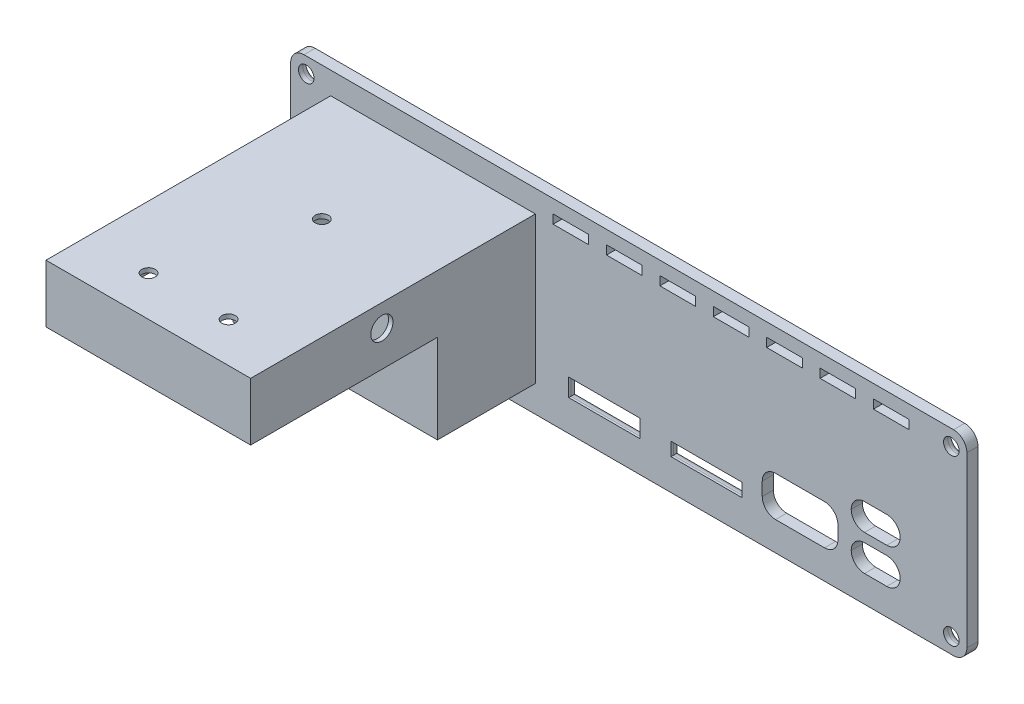
SolidWorks part; units mm, degrees
ref_plane "Front Plane" through (0, 0, 0) normal (0, 0, 1) x (1, 0, 0)
ref_plane "Top Plane" through (0, 0, 0) normal (0, 1, 0) x (1, 0, 0)
ref_plane "Right Plane" through (0, 0, 0) normal (1, 0, 0) x (0, 0, -1)
sketch "Sketch1" plane through (0, 0, 0) normal (0, 0, 1) x (1, 0, 0)
  line L1 (76, -22) -> (-76, -22)
  line L2 (76, -22) -> (76, 22)
  line L3 (76, 22) -> (-76, 22)
  line L4 (-76, -22) -> (-76, 22)
  line L5 (76, -22) -> (-76, 22) construction
  line L6 (76, 22) -> (-76, -22) construction
  point P0 (0, 0)
  dimension "D1" = 152
  dimension "D2" = 44
extrude "main_body" add sketch "Sketch1" along normal blind 2.5
fillet "body_corners" radius 3 4 edges at (-76, -22, 1.25) (76, -22, 1.25) (76, 22, 1.25) (-76, 22, 1.25)
sketch "Sketch2" plane through (0, 0, 2.5) normal (0, 0, 1) x (1, 0, 0)
  line L0 (-76, 18.5) -> (76, 18.5) construction
  line L1 (-76, 19) -> (-76, -19) construction
  line L2 (76, -19) -> (76, 19) construction
  line L3 (-72.5, 22) -> (-72.5, -22) construction
  line L4 (-76, -18.5) -> (76, -18.5) construction
  line L8 (73, 22) -> (-73, 22) construction
  line L9 (72.5, 22) -> (72.5, -22) construction
  line L10 (-73, -22) -> (73, -22) construction
  circle A1 centre (-72.5, -18.5) radius 1.75
  circle A2 centre (72.5, 18.5) radius 1.75
  circle A3 centre (72.5, -18.5) radius 1.75
  circle A4 centre (-72.5, 18.5) radius 1.75
  dimension "D5" = 3.5
  dimension "D6" = 3.5
  dimension "D7" = 3.5
  dimension "D8" = 3.5
  dimension "D1" = 3.5
  dimension "D2" = 3.5
  dimension "D3" = 3.5
  dimension "D4" = 3.5
extrude "mounting_holes" cut sketch "Sketch2" against normal through all
fillet "bolt_heads" radius 1.5 4 edges at (-70.75, -18.5, 0) (-70.75, 18.5, 0) (74.25, -18.5, 0) (74.25, 18.5, 0)
sketch "Sketch3" plane through (0, 0, 2.5) normal (0, 0, 1) x (1, 0, 0)
  line L0 (-76, 5) -> (76, 5) construction
  line L1 (-76, 19) -> (-76, -19) construction
  line L2 (76, -19) -> (76, 19) construction
  line L3 (73, 22) -> (-73, 22) construction
  line L4 (-73, -22) -> (73, -22) construction
  line L5 (0, 22) -> (0, -22) construction
  line L6 (76, -19) -> (76, 19) construction
  line L8 (50, -2) -> (61, -2)
  line L10 (50, -2) -> (50, -8)
  line L11 (50, -8) -> (61, -8)
  line L13 (61, -2) -> (61, -8)
  line L14 (50, -2) -> (61, -8) construction
  line L16 (50, -8) -> (61, -2) construction
  line L17 (30, -6.5) -> (47, -6.5)
  line L18 (30, -6.5) -> (30, -15.5)
  line L19 (30, -15.5) -> (47, -15.5)
  line L20 (47, -6.5) -> (47, -15.5)
  line L21 (30, -6.5) -> (47, -15.5) construction
  line L22 (30, -15.5) -> (47, -6.5) construction
  line L23 (50, -10) -> (61, -10)
  line L24 (50, -10) -> (50, -16)
  line L25 (50, -16) -> (61, -16)
  line L26 (61, -10) -> (61, -16)
  line L27 (50, -10) -> (61, -16) construction
  line L28 (50, -16) -> (61, -10) construction
  line L29 (9.5, -12) -> (25.5, -12)
  line L30 (9.5, -12) -> (9.5, -15)
  line L31 (9.5, -15) -> (25.5, -15)
  line L32 (25.5, -12) -> (25.5, -15)
  line L33 (9.5, -12) -> (25.5, -15) construction
  line L34 (9.5, -15) -> (25.5, -12) construction
  line L35 (-13.5, -11) -> (2.5, -11)
  line L36 (-13.5, -11) -> (-13.5, -15)
  line L37 (-13.5, -15) -> (2.5, -15)
  line L38 (2.5, -11) -> (2.5, -15)
  line L39 (-13.5, -11) -> (2.5, -15) construction
  line L40 (-13.5, -15) -> (2.5, -11) construction
  point P15 (-5.5, -13)
  point P34 (55.5, -13)
  point P36 (55.5, -5)
  point P41 (38.5, -11)
  point P49 (55.5, -16)
  point P51 (17.5, -13.5)
  dimension "D7" = 73.5
  dimension "D8" = 7
  dimension "D9" = 4
  dimension "D10" = 16
  dimension "D12" = 50.5
  dimension "D13" = 6
  dimension "D14" = 11
  dimension "D15" = 29
  dimension "D1" = 17
  dimension "D16" = 6
  dimension "D17" = 15
  dimension "D18" = 15
  dimension "D19" = 11
  dimension "D20" = 6
  dimension "D21" = 17
  dimension "D22" = 9
  dimension "D23" = 8
  dimension "D25" = 14
  dimension "D26" = 6.5
  dimension "D28" = 7
  dimension "D30" = 3
  dimension "D31" = 16
extrude "connectors" cut sketch "Sketch3" against normal through all
fillet "usb_host_corners" radius 3 4 edges at (47, -15.5, 1.25) (47, -6.5, 1.25) (30, -15.5, 1.25) (30, -6.5, 1.25)
fillet "usb_dfu_corners" radius 3 8 edges at (61, -2, 1.25) (61, -8, 1.25) (50, -8, 1.25) (50, -2, 1.25) (61, -10, 1.25) (61, -16, 1.25) (50, -16, 1.25) (50, -10, 1.25)
fillet "sd_rot_corners" radius 2 8 edges at (-5.5, -11, 0) (-13.5, -13, 0) (-5.5, -15, 0) (2.5, -13, 0) (9.5, -13.5, 0) (25.5, -13.5, 0) (17.5, -15, 0) (17.5, -12, 0)
sketch "Sketch4" plane through (0, 0, 2.5) normal (0, 0, 1) x (1, 0, 0)
  line L0 (-76, 19) -> (-76, -19) construction
  line L1 (-67, 17) -> (-21, 17)
  line L2 (-67, 17) -> (-67, -16)
  line L3 (-67, -16) -> (-21, -16)
  line L4 (-21, 17) -> (-21, -16)
  line L5 (-67, 17) -> (-21, -16) construction
  line L6 (-67, -16) -> (-21, 17) construction
  line L7 (-73, -22) -> (73, -22) construction
  point P0 (-44, 0.5)
  dimension "D1" = 9
  dimension "D2" = 6
  dimension "D3" = 33
  dimension "D4" = 46
extrude "keyer" add sketch "Sketch4" along normal blind 22
sketch "Sketch5" plane through (0, 0, 24.5) normal (0, 0, 1) x (1, 0, 0)
  line L0 (-67, -16) -> (-21, 17) construction
  line L1 (-21, 17) -> (-67, 17) construction
  line L2 (-22, -15) -> (-66, -15)
  line L3 (-67, 17) -> (-21, -16) construction
  line L4 (-22, -15) -> (-22, 16)
  line L5 (-22, 16) -> (-66, 16)
  line L6 (-66, -15) -> (-66, 16)
  line L7 (-22, -15) -> (-66, 16) construction
  line L8 (-22, 16) -> (-66, -15) construction
  line L9 (-21, -16) -> (-21, 17) construction
  point P4 (-44, 0.5)
  dimension "D1" = 1
  dimension "D2" = 1
extrude "keyer_cut" cut sketch "Sketch5" along normal blind 24 from offset 25 offset against normal yes
sketch "Sketch6" plane through (0, 0, 0) normal (0, 0, -1) x (-1, 0, 0)
  line L1 (69, -20) -> (-69, -20)
  line L2 (69, -20) -> (69, 20)
  line L3 (69, 20) -> (-69, 20)
  line L4 (-69, -20) -> (-69, 20)
  line L5 (69, -20) -> (-69, 20) construction
  line L6 (69, 20) -> (-69, -20) construction
  point P0 (0, 0)
  dimension "D1" = 138
  dimension "D2" = 40
extrude "paint_slot" cut sketch "Sketch6" against normal blind 0.01
fillet "paint_slot_corners" radius 5 4 edges at (-69, -20, 0.005) (-69, 20, 0.005) (69, -20, 0.005) (69, 20, 0.005)
sketch "Sketch7" plane through (0, 0, 0.01) normal (0, 0, -1) x (-1, 0, 0)
  line L0 (-69, 18) -> (69, 18) construction
  line L1 (-69, 15) -> (-69, -15) construction
  line L2 (69, -15) -> (69, 15) construction
  line L3 (64, 20) -> (-64, 20) construction
  line L4 (-76, -19) -> (-76, 19) construction
  line L5 (-55, 17) -> (-63, 17)
  line L6 (-55, 17) -> (-55, 19)
  line L7 (-55, 19) -> (-63, 19)
  line L8 (-63, 17) -> (-63, 19)
  line L9 (-55, 17) -> (-63, 19) construction
  line L10 (-55, 19) -> (-63, 17) construction
  line L11 (-43, 17) -> (-51, 17)
  line L12 (-43, 17) -> (-43, 19)
  line L13 (-43, 19) -> (-51, 19)
  line L14 (-51, 17) -> (-51, 19)
  line L15 (-43, 17) -> (-51, 19) construction
  line L16 (-43, 19) -> (-51, 17) construction
  line L17 (-31, 17) -> (-39, 17)
  line L18 (-31, 17) -> (-31, 19)
  line L19 (-31, 19) -> (-39, 19)
  line L20 (-39, 17) -> (-39, 19)
  line L21 (-31, 17) -> (-39, 19) construction
  line L22 (-31, 19) -> (-39, 17) construction
  line L23 (-19, 17) -> (-27, 17)
  line L24 (-19, 17) -> (-19, 19)
  line L25 (-19, 19) -> (-27, 19)
  line L26 (-27, 17) -> (-27, 19)
  line L27 (-19, 17) -> (-27, 19) construction
  line L28 (-19, 19) -> (-27, 17) construction
  line L29 (-7, 17) -> (-15, 17)
  line L30 (-7, 17) -> (-7, 19)
  line L31 (-7, 19) -> (-15, 19)
  line L32 (-15, 17) -> (-15, 19)
  line L33 (-7, 17) -> (-15, 19) construction
  line L34 (-7, 19) -> (-15, 17) construction
  line L35 (5, 17) -> (-3, 17)
  line L36 (5, 17) -> (5, 19)
  line L37 (5, 19) -> (-3, 19)
  line L38 (-3, 17) -> (-3, 19)
  line L39 (5, 17) -> (-3, 19) construction
  line L40 (5, 19) -> (-3, 17) construction
  line L41 (17, 17) -> (9, 17)
  line L42 (17, 17) -> (17, 19)
  line L43 (17, 19) -> (9, 19)
  line L44 (9, 17) -> (9, 19)
  line L45 (17, 17) -> (9, 19) construction
  line L46 (17, 19) -> (9, 17) construction
  point P8 (-59, 18)
  point P13 (-47, 18)
  point P18 (-35, 18)
  point P23 (-23, 18)
  point P28 (-11, 18)
  point P33 (1, 18)
  point P38 (13, 18)
  dimension "D1" = 2
  dimension "D2" = 8
  dimension "D3" = 2
  dimension "D4" = 13
  dimension "D5" = 4
  dimension "D6" = 8
  dimension "D7" = 4
  dimension "D8" = 4
  dimension "D9" = 4
  dimension "D10" = 8
  dimension "D11" = 2
  dimension "D12" = 2
  dimension "D13" = 8
  dimension "D14" = 2
  dimension "D15" = 8
  dimension "D16" = 2
  dimension "D17" = 4
  dimension "D18" = 8
  dimension "D19" = 2
  dimension "D20" = 4
  dimension "D21" = 8
  dimension "D22" = 2
extrude "batt_fan_exhaust" cut sketch "Sketch7" against normal through all
sketch "Sketch8" plane through (0, 0, 24.5) normal (0, 0, 1) x (1, 0, 0)
  line L0 (-66, 17) -> (-66, -16) construction
  line L1 (-21, 17) -> (-67, 17) construction
  line L2 (-67, -16) -> (-21, -16) construction
  line L3 (-67, 16) -> (-21, 16) construction
  line L4 (-22, 17) -> (-22, -16) construction
  line L5 (-67, -16) -> (-21, -16) construction
  line L6 (-67, 17) -> (-67, -16) construction
  line L7 (-21, -16) -> (-21, 17) construction
  line L9 (-22, 16) -> (-66, 16)
  line L10 (-22, 16) -> (-22, 5)
  line L11 (-22, 5) -> (-66, 5)
  line L12 (-66, 16) -> (-66, 5)
  dimension "D1" = 1
  dimension "D2" = 1
  dimension "D3" = 1
  dimension "D4" = 11
extrude "back_cut" cut sketch "Sketch8" against normal blind 20
sketch "Sketch9" plane through (0, 0, 24.5) normal (0, 0, 1) x (1, 0, 0)
  line L0 (-21, -16) -> (-21, 17) construction
  line L1 (-67, 17) -> (-21, 17)
  line L2 (-67, 17) -> (-67, 4)
  line L3 (-67, 4) -> (-21, 4)
  line L4 (-21, 17) -> (-21, 4)
  line L6 (-66, 16) -> (-22, 16)
  line L7 (-66, 16) -> (-66, 5)
  line L8 (-66, 5) -> (-22, 5)
  line L9 (-22, 16) -> (-22, 5)
  dimension "D1" = 1
extrude "back_ext" add sketch "Sketch9" along normal blind 42
sketch "Sketch10" plane through (0, 4, 0) normal (0, -1, 0) x (1, 0, 0)
  line L6 (-21, 24.5) -> (-67, 66.5) construction
  line L8 (-22.0952, 65.5) -> (-65.9048, 65.5)
  line L9 (-21, 66.5) -> (-67, 24.5) construction
  line L10 (-22.0952, 65.5) -> (-22.0952, 25.5)
  line L11 (-22.0952, 25.5) -> (-65.9048, 25.5)
  line L12 (-65.9048, 65.5) -> (-65.9048, 25.5)
  line L13 (-22.0952, 65.5) -> (-65.9048, 25.5) construction
  line L14 (-22.0952, 25.5) -> (-65.9048, 65.5) construction
  point P2 (-44, 45.5)
  dimension "D1" = 40
extrude "access_hole" cut sketch "Sketch10" against normal blind 1
sketch "Sketch11" plane through (0, 16, 0) normal (0, -1, 0) x (1, 0, 0)
  line L0 (-22.0952, 65.5) -> (-65.9048, 65.5) construction
  line L5 (-66, 65.5) -> (-22, 65.5)
  line L6 (-66, 65.5) -> (-66, 66.5)
  line L7 (-66, 66.5) -> (-22, 66.5)
  line L8 (-22, 65.5) -> (-22, 66.5)
  line L9 (-67, 66.5) -> (-21, 66.5) construction
  line L10 (-67, 66.5) -> (-67, 24.5) construction
  line L11 (-21, 66.5) -> (-21, 24.5) construction
  dimension "D1" = 1
  dimension "D2" = 1
extrude "back_closer" add sketch "Sketch11" along normal blind 11
sketch "Sketch12" plane through (0, 16, 0) normal (0, -1, 0) x (1, 0, 0)
  line L0 (-65.9048, 57.5) -> (-22, 57.5) construction
  line L1 (-65.9048, 65.5) -> (-65.9048, 25.5) construction
  line L2 (-22, 65.5) -> (-22, 0.01) construction
  line L3 (-44, 65.5) -> (-44, 0) construction
  line L4 (-22.0952, 65.5) -> (-65.9048, 65.5) construction
  line L5 (-73, 0) -> (73, 0) construction
  line L6 (-66, 65.5) -> (-22, 65.5) construction
  circle A0 centre (-52.9524, 57.5) radius 1.5
  circle A1 centre (-34.9524, 57.5) radius 1.5
  circle A2 centre (-44, 27.5) radius 1.5
  point P20 (-43.9524, 57.5)
  dimension "D2" = 3
  dimension "D3" = 3
  dimension "D4" = 3
  dimension "D1" = 8
  dimension "D5" = 9
  dimension "D6" = 9
  dimension "D7" = 30
extrude "paddle_holes" cut sketch "Sketch12" against normal through all
sketch "Sketch13" plane through (0, 16, 0) normal (0, -1, 0) x (1, 0, 0)
  line L0 (-55.9048, 65.5) -> (-55.9048, 25.5) construction
  line L1 (-66, 65.5) -> (-22, 65.5) construction
  line L2 (-65.9048, 25.5) -> (-22.0952, 25.5) construction
  line L3 (-65.9048, 65.5) -> (-65.9048, 25.5) construction
  line L4 (-32.0952, 65.5) -> (-32.0952, 25.5) construction
  line L5 (-22.0952, 25.5) -> (-22.0952, 65.5) construction
  line L6 (-44, 27.5) -> (-55.9048, 27.5) construction
  line L7 (-53.6548, 40) -> (-58.1548, 40)
  line L8 (-53.6548, 40) -> (-53.6548, 34)
  line L9 (-53.6548, 34) -> (-58.1548, 34)
  line L10 (-58.1548, 40) -> (-58.1548, 34)
  line L11 (-53.6548, 40) -> (-58.1548, 34) construction
  line L12 (-53.6548, 34) -> (-58.1548, 40) construction
  line L13 (-29.8452, 40) -> (-34.3452, 40)
  line L14 (-29.8452, 40) -> (-29.8452, 34)
  line L15 (-29.8452, 34) -> (-34.3452, 34)
  line L16 (-34.3452, 40) -> (-34.3452, 34)
  line L17 (-29.8452, 40) -> (-34.3452, 34) construction
  line L18 (-29.8452, 34) -> (-34.3452, 40) construction
  line L19 (-34.9524, 57.5) -> (-52.9524, 57.5) construction
  point P12 (-55.9048, 37)
  point P17 (-32.0952, 37)
  dimension "D1" = 10
  dimension "D2" = 10
  dimension "D3" = 6
  dimension "D4" = 6
  dimension "D5" = 4.5
  dimension "D6" = 4.5
  dimension "D7" = 19.3095
  dimension "D8" = 9.5
  dimension "D9" = 9.5
  dimension "D10" = 20.5
extrude "pilars" add sketch "Sketch13" along normal blind 7
sketch "Sketch14" plane through (-34.3452, 0, 0) normal (-1, 0, 0) x (0, 0, 1)
  line L0 (40, 16) -> (34, 16) construction
  line L1 (34, 9) -> (34, 16) construction
  circle A0 centre (37, 12) radius 1.5
  dimension "D2" = 3
  dimension "D1" = 4
  dimension "D3" = 3
extrude "pilar_hole" cut sketch "Sketch14" against normal blind 47 from offset 33
sketch "Sketch15" plane through (-67, 0, 0) normal (-1, 0, 0) x (0, 0, 1)
  line L0 (37, 12) -> (66.5, 12) construction
  line L1 (66.5, 17) -> (66.5, 4) construction
  circle A0 centre (46, 12) radius 2.5
  circle A1 centre (37, 12) radius 2.5
  dimension "D1" = 5
  dimension "D2" = 5
  dimension "D3" = 9
extrude "adj_holes" cut sketch "Sketch15" against normal blind 1
sketch "Sketch16" plane through (-21, 0, 0) normal (1, 0, 0) x (0, 0, -1)
  circle A0 centre (-37, 12) radius 2.5
  dimension "D1" = 5
extrude "adj_hole1" cut sketch "Sketch16" against normal blind 1
